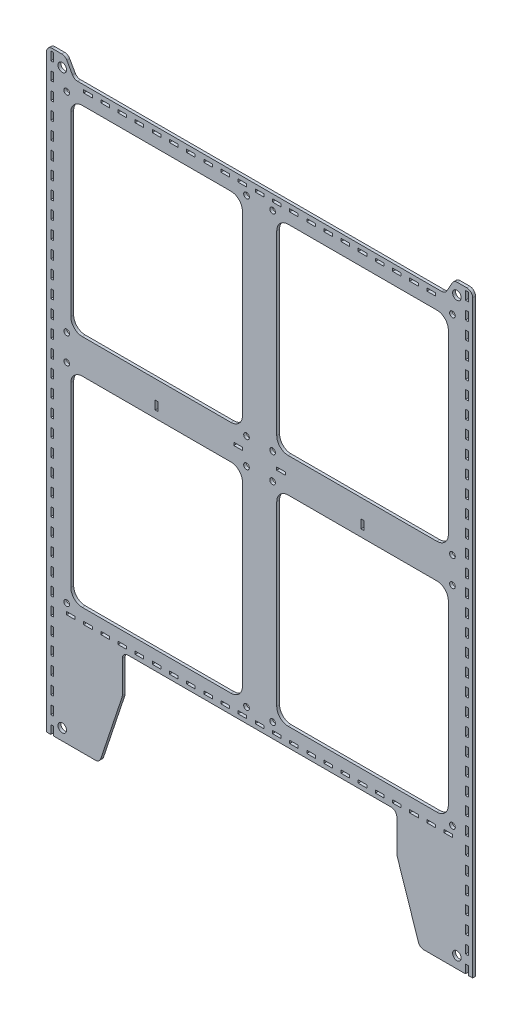
SolidWorks part; units mm, degrees
material "ABS"
ref_plane "Front Plane" through (0, 0, 0) normal (0, 0, 1) x (1, 0, 0)
ref_plane "Top Plane" through (0, 0, 0) normal (0, 1, 0) x (1, 0, 0)
ref_plane "Right Plane" through (0, 0, 0) normal (1, 0, 0) x (0, 0, -1)
sketch "Sketch1" plane through (0, 0, 0) normal (0, 0, 1) x (1, 0, 0)
  line L1 (-114.3, -127) -> (114.3, -127)
  line L2 (-114.3, -127) -> (-114.3, 127)
  line L3 (-114.3, 127) -> (114.3, 127)
  line L4 (114.3, -127) -> (114.3, 127)
  line L5 (-114.3, -127) -> (114.3, 127) construction
  line L6 (-114.3, 127) -> (114.3, -127) construction
  point P0 (0, 0)
  dimension "D1" = 254
  dimension "D2" = 228.6
extrude "Boss-Extrude1" add sketch "Sketch1" along normal mid plane 1.5875
sketch "Sketch2" plane through (0, 0, 0.7937) normal (0, 0, 1) x (1, 0, 0)
  line L0 (-114.3, -127) -> (-114.3, -190.5)
  line L1 (-114.3, -190.5) -> (-88.9, -190.5)
  line L2 (-88.9, -190.5) -> (-76.2, -152.4)
  line L3 (-76.2, -152.4) -> (-76.2, -127)
  line L4 (-114.3, -127) -> (114.3, -127) construction
  line L5 (-76.2, -127) -> (-114.3, -127)
  line L6 (114.3, -127) -> (114.3, -190.5)
  line L7 (114.3, -190.5) -> (88.9, -190.5)
  line L8 (88.9, -190.5) -> (76.2, -152.4)
  line L9 (76.2, -152.4) -> (76.2, -127)
  line L10 (114.3, -127) -> (76.2, -127)
  line L11 (-114.3, 127) -> (-114.3, 139.7)
  line L12 (-114.3, 139.7) -> (-107.95, 139.7)
  line L13 (-107.95, 139.7) -> (-101.6, 128.5875)
  line L14 (114.3, 127) -> (-114.3, 127) construction
  line L15 (-101.6, 127) -> (-114.3, 127)
  line L16 (114.3, 127) -> (114.3, 139.7)
  line L17 (114.3, 139.7) -> (107.95, 139.7)
  line L18 (-101.6, 128.5875) -> (-101.6, 127)
  line L19 (101.6, 127) -> (114.3, 127)
  line L20 (107.95, 139.7) -> (101.6, 128.5875)
  line L21 (101.6, 128.5875) -> (101.6, 127)
  dimension "D1" = 63.5
  dimension "D2" = 25.4
  dimension "D3" = 25.4
  dimension "D4" = 38.1
  dimension "D5" = 12.7
  dimension "D6" = 6.35
  dimension "D7" = 12.7
  dimension "D8" = 1.5875
extrude "Boss-Extrude2" add sketch "Sketch2" against normal up to surface (1.5875 mm away) up to face at (0, 0, -0.7937)
sketch "Sketch7" plane through (0, 0, 0.7937) normal (0, 0, 1) x (1, 0, 0)
  line L0 (-114.3, 139.7) -> (-118.2688, 139.7)
  line L1 (-118.2688, 139.7) -> (-118.2688, 130.175)
  line L2 (-118.2688, 130.175) -> (-114.3, 130.175)
  line L3 (-114.3, 139.7) -> (-114.3, -190.5) construction
  line L4 (-114.3, 130.175) -> (-114.3, 133.35)
  line L5 (-114.3, 133.35) -> (-115.8875, 133.35)
  line L6 (-115.8875, 133.35) -> (-115.8875, 138.1125)
  line L7 (-115.8875, 138.1125) -> (-114.3, 138.1125)
  line L8 (-114.3, 138.1125) -> (-114.3, 139.7)
  dimension "D1" = 1.5875
  dimension "D2" = 3.175
  dimension "D3" = 2.3813
  dimension "D4" = 1.5875
  dimension "D5" = 4.7625
extrude "Boss-Extrude6" add sketch "Sketch7" against normal up to surface (1.5875 mm away) up to face at (1.5875, -16.5199, -0.7937)
pattern_linear "LPattern3" count 34 spacing 9.525 along (0, -1, 0) of "Boss-Extrude6"
sketch "Sketch10" plane through (0, 0, 0.7937) normal (0, 0, 1) x (1, 0, 0)
  line L0 (-118.2688, -190.5) -> (-115.8875, -190.5)
  line L1 (-115.8875, -190.5) -> (-115.8875, -185.7375)
  line L2 (-115.8875, -185.7375) -> (-114.3, -185.7375)
  line L3 (-114.3, -184.15) -> (-114.3, -190.5) construction
  line L4 (-114.3, -185.7375) -> (-114.3, -184.15)
  line L5 (-114.3, -184.15) -> (-118.2688, -184.15)
  line L6 (-118.2688, -184.15) -> (-118.2688, -190.5)
  line L7 (-115.8875, -180.975) -> (-115.8875, -176.2125) construction
  line L8 (-114.3, -190.5) -> (-88.9, -190.5) construction
  dimension "D1" = 1.5875
extrude "Boss-Extrude9" add sketch "Sketch10" against normal up to surface (1.5875 mm away) up to face at (-115.0938, 126.2062, -0.7937)
mirror "Mirror3" about plane through (0, 0, 0) normal (1, 0, 0) of "Boss-Extrude9", "LPattern3"
sketch "Sketch8" plane through (0, 0, 0.7937) normal (0, 0, 1) x (1, 0, 0)
  line L0 (-101.6, 130.9688) -> (-92.075, 130.9688)
  line L1 (-92.075, 130.9688) -> (-92.075, 127)
  line L2 (101.6, 127) -> (-101.6, 127) construction
  line L3 (-92.075, 127) -> (-92.8688, 127)
  line L4 (-92.8688, 127) -> (-92.8688, 128.5875)
  line L5 (-92.8688, 128.5875) -> (-97.6313, 128.5875)
  line L6 (-97.6313, 128.5875) -> (-97.6313, 127)
  line L7 (-97.6313, 127) -> (-101.6, 127)
  line L8 (-101.6, 127) -> (-101.6, 130.9688)
  dimension "D1" = 3.9688
  dimension "D2" = 1.5875
  dimension "D3" = 4.7625
  dimension "D4" = 2.3813
  dimension "D5" = 0.7937
extrude "Boss-Extrude7" add sketch "Sketch8" against normal up to surface (1.5875 mm away) up to face at (1.0583, -73.7195, -0.7937)
pattern_linear "LPattern4" count 22 spacing 9.525 along (1, 0, 0) of "Boss-Extrude7"
sketch "Sketch9" plane through (0, 0, 0.7937) normal (0, 0, 1) x (1, 0, 0)
  line L0 (-101.6, 130.9688) -> (-102.9607, 130.9688)
  line L1 (-101.6, 128.5875) -> (-107.95, 139.7) construction
  line L2 (-102.9607, 130.9688) -> (-101.6, 128.5875)
  line L3 (-101.6, 128.5875) -> (-101.6, 130.9688)
extrude "Boss-Extrude8" add sketch "Sketch9" against normal up to surface (1.5875 mm away) up to face at (-85.1297, 127.7937, -0.7937)
mirror "Mirror4" about plane through (0, 0, 0) normal (0, 1, 0) of "LPattern4"
sketch "Sketch13" plane through (0, 0, 0.7937) normal (0, 0, 1) x (1, 0, 0)
  line L0 (-73.8188, -128.5875) -> (-73.8188, -127) construction
  line L1 (-76.2, -127) -> (-78.5813, -127)
  line L2 (-76.2, -127) -> (-76.2, -128.5875)
  line L3 (-76.2, -128.5875) -> (-78.5813, -128.5875)
  line L4 (-78.5813, -127) -> (-78.5813, -128.5875)
  line L5 (-83.3438, -127) -> (-88.1063, -127)
  line L6 (-83.3438, -127) -> (-83.3438, -128.5875)
  line L7 (-83.3438, -128.5875) -> (-88.1063, -128.5875)
  line L8 (-88.1063, -127) -> (-88.1063, -128.5875)
  line L9 (-76.2, -128.5875) -> (-73.8188, -128.5875) construction
  line L11 (-92.8688, -127) -> (-97.6313, -127)
  line L12 (-92.8688, -127) -> (-92.8688, -128.5875)
  line L13 (-92.8688, -128.5875) -> (-97.6313, -128.5875)
  line L14 (-97.6313, -127) -> (-97.6313, -128.5875)
  line L15 (-102.3938, -127) -> (-107.1563, -127)
  line L16 (-102.3938, -127) -> (-102.3938, -128.5875)
  line L17 (-102.3938, -128.5875) -> (-107.1563, -128.5875)
  line L18 (-107.1563, -127) -> (-107.1563, -128.5875)
  dimension "D1" = 4.7625
  dimension "D2" = 4.7625
  dimension "D3" = 4.7625
  dimension "D4" = 4.7625
  dimension "D5" = 4.7625
extrude "Cut-Extrude2" cut sketch "Sketch13" against normal through all
mirror "Mirror5" about plane through (0, 0, 0) normal (1, 0, 0) of "Cut-Extrude2"
sketch "Sketch18" plane through (0, 0, 0.7937) normal (0, 0, 1) x (1, 0, 0)
  line L1 (-0.7938, -5.5562) -> (0.7938, -5.5562) construction
  line L2 (-0.7938, -5.5562) -> (-0.7938, -0.7937) construction
  line L3 (-0.7938, -0.7937) -> (0.7938, -0.7937) construction
  line L4 (0.7938, -5.5562) -> (0.7938, -0.7937) construction
  line L5 (-0.7938, -5.5562) -> (0.7938, -0.7937) construction
  line L6 (-0.7938, -0.7937) -> (0.7938, -5.5562) construction
  line L7 (56.3563, -5.5563) -> (57.9437, -5.5563)
  line L8 (56.3563, -5.5563) -> (56.3563, -0.7938)
  line L9 (56.3563, -0.7938) -> (57.9437, -0.7938)
  line L10 (57.9437, -5.5563) -> (57.9437, -0.7938)
  line L11 (56.3563, -5.5563) -> (57.9437, -0.7938) construction
  line L12 (56.3563, -0.7938) -> (57.9437, -5.5563) construction
  line L13 (-56.3563, -5.5563) -> (-57.9438, -5.5563)
  line L14 (-56.3563, -5.5563) -> (-56.3563, -0.7938)
  line L15 (-56.3563, -0.7938) -> (-57.9438, -0.7938)
  line L16 (-57.9438, -5.5563) -> (-57.9438, -0.7938)
  line L17 (-56.3563, -5.5563) -> (-57.9438, -0.7938) construction
  line L18 (-56.3563, -0.7938) -> (-57.9438, -5.5563) construction
  point P0 (0, -3.175)
  point P6 (57.15, -3.175)
  point P11 (-57.15, -3.175)
  dimension "D1" = 1.5875
  dimension "D2" = 4.7625
  dimension "D3" = 57.15
  dimension "D4" = 57.15
  dimension "D5" = 0.7937
extrude "Cut-Extrude4" cut sketch "Sketch18" against normal through all
sketch "Sketch19" plane through (0, 0, 0.7937) normal (0, 0, 1) x (1, 0, 0)
  line L0 (-9.525, -9.525) -> (9.525, 9.525) construction
  line L1 (-104.775, 9.525) -> (-9.525, 9.525)
  line L2 (-104.775, 9.525) -> (-104.775, 120.65)
  line L3 (-104.775, 120.65) -> (-9.525, 120.65)
  line L4 (-9.525, 9.525) -> (-9.525, 120.65)
  line L5 (-104.775, 9.525) -> (-9.525, 120.65) construction
  line L6 (-104.775, 120.65) -> (-9.525, 9.525) construction
  line L7 (9.525, 9.525) -> (104.775, 9.525)
  line L8 (9.525, 9.525) -> (9.525, 120.65)
  line L9 (9.525, 120.65) -> (104.775, 120.65)
  line L10 (104.775, 9.525) -> (104.775, 120.65)
  line L11 (9.525, 9.525) -> (104.775, 120.65) construction
  line L12 (9.525, 120.65) -> (104.775, 9.525) construction
  line L13 (9.525, -9.525) -> (104.775, -9.525)
  line L14 (9.525, -9.525) -> (9.525, -120.65)
  line L15 (9.525, -120.65) -> (104.775, -120.65)
  line L16 (104.775, -9.525) -> (104.775, -120.65)
  line L17 (9.525, -9.525) -> (104.775, -120.65) construction
  line L18 (9.525, -120.65) -> (104.775, -9.525) construction
  line L19 (-9.525, -9.525) -> (-104.775, -9.525)
  line L20 (-9.525, -9.525) -> (-9.525, -120.65)
  line L21 (-9.525, -120.65) -> (-104.775, -120.65)
  line L22 (-104.775, -9.525) -> (-104.775, -120.65)
  line L23 (-9.525, -9.525) -> (-104.775, -120.65) construction
  line L24 (-9.525, -120.65) -> (-104.775, -9.525) construction
  point P0 (-57.15, 65.0875)
  point P5 (57.15, 65.0875)
  point P10 (57.15, -65.0875)
  point P15 (-57.15, -65.0875)
  dimension "D1" = 209.55
  dimension "D2" = 241.3
  dimension "D3" = 19.05
  dimension "D4" = 19.05
extrude "Cut-Extrude5" cut sketch "Sketch19" against normal through all
fillet "Fillet1" radius 6.35 16 edges at (-104.775, -120.65, 0) (-9.525, -120.65, 0) (-9.525, -9.525, 0) (-104.775, -9.525, 0) (104.775, -9.525, 0) (9.525, -9.525, 0) (9.525, -120.65, 0) (104.775, -120.65, 0) (104.775, 120.65, 0) (9.525, 120.65, 0) (9.525, 9.525, 0) (104.775, 9.525, 0) (-9.525, 120.65, 0) (-104.775, 120.65, 0) (-104.775, 9.525, 0) (-9.525, 9.525, 0)
sketch "Sketch20" plane through (0, 0, 0.7937) normal (0, 0, 1) x (1, 0, 0)
  line L0 (-9.525, 0.7938) -> (9.525, -0.7938) construction
  line L1 (-14.2875, -0.7938) -> (-9.525, -0.7938)
  line L2 (-14.2875, -0.7938) -> (-14.2875, 0.7938)
  line L3 (-14.2875, 0.7938) -> (-9.525, 0.7938)
  line L4 (-9.525, -0.7938) -> (-9.525, 0.7938)
  line L5 (-14.2875, -0.7938) -> (-9.525, 0.7938) construction
  line L6 (-14.2875, 0.7938) -> (-9.525, -0.7938) construction
  line L7 (9.525, -0.7938) -> (14.2875, -0.7938)
  line L8 (9.525, -0.7938) -> (9.525, 0.7938)
  line L9 (9.525, 0.7938) -> (14.2875, 0.7938)
  line L10 (14.2875, -0.7938) -> (14.2875, 0.7938)
  line L11 (9.525, -0.7938) -> (14.2875, 0.7938) construction
  line L12 (9.525, 0.7938) -> (14.2875, -0.7938) construction
  point P0 (-11.9062, 0)
  point P5 (11.9062, 0)
  dimension "D1" = 4.7625
  dimension "D2" = 19.05
  dimension "D3" = 1.5875
extrude "Cut-Extrude6" cut sketch "Sketch20" against normal through all
sketch "Sketch21" plane through (0, 0, 0.7937) normal (0, 0, 1) x (1, 0, 0)
  line L1 (-109.5375, -184.15) -> (109.5375, -184.15) construction
  line L2 (-109.5375, -184.15) -> (-109.5375, 133.35) construction
  line L3 (-109.5375, 133.35) -> (109.5375, 133.35) construction
  line L4 (109.5375, -184.15) -> (109.5375, 133.35) construction
  line L5 (-109.5375, -184.15) -> (109.5375, 133.35) construction
  line L6 (-109.5375, 133.35) -> (109.5375, -184.15) construction
  line L8 (-107.95, 139.7) -> (-118.2688, 139.7) construction
  line L9 (-114.3, 138.1125) -> (-114.3, 133.35) construction
  line L10 (-114.3, -190.5) -> (-88.9, -190.5) construction
  circle A0 centre (-109.5375, 133.35) radius 2.3813
  circle A1 centre (-109.5375, -184.15) radius 2.3813
  circle A2 centre (109.5375, 133.35) radius 2.3813
  circle A3 centre (109.5375, -184.15) radius 2.3813
  point P0 (0, -25.4)
  dimension "D2" = 4.7625
  dimension "D1" = 6.35
  dimension "D3" = 4.7625
  dimension "D4" = 6.35
extrude "Cut-Extrude7" cut sketch "Sketch21" against normal through all
sketch "Sketch22" plane through (0, 0, 0.7937) normal (0, 0, 1) x (1, 0, 0)
  line L0 (-107.061, 15.875) -> (-107.061, 7.239) construction
  line L1 (-107.061, 7.239) -> (-98.425, 7.239) construction
  line L2 (-15.875, 7.239) -> (-7.239, 7.239) construction
  line L3 (-7.239, 7.239) -> (-7.239, 15.875) construction
  line L4 (-7.239, 15.875) -> (-6.626, 15.9261)
  line L5 (-7.239, 114.3) -> (-7.239, 122.936) construction
  line L6 (-7.239, 122.936) -> (-15.875, 122.936) construction
  line L7 (-98.425, 122.936) -> (-107.061, 122.936) construction
  line L8 (-107.061, 122.936) -> (-107.061, 114.3) construction
  line L9 (0, 130.9688) -> (0, -130.9688) construction
  line L10 (102.9607, 130.9688) -> (-102.9607, 130.9688) construction
  line L11 (76.2, -130.9688) -> (-76.2, -130.9688) construction
  line L12 (-118.2688, 0) -> (118.2688, 0) construction
  line L14 (-118.2688, 139.7) -> (-118.2688, -190.5) construction
  line L16 (118.2688, 139.7) -> (118.2688, -190.5) construction
  line L25 (-98.425, 7.239) -> (-15.875, 7.239)
  line L26 (-7.239, 15.875) -> (-7.239, 114.3)
  line L27 (-15.875, 122.936) -> (-98.425, 122.936)
  line L28 (-107.061, 114.3) -> (-107.061, 15.875)
  line L29 (-98.425, 7.239) -> (-15.875, 7.239) construction
  line L30 (-7.239, 15.875) -> (-7.239, 114.3) construction
  line L31 (-15.875, 122.936) -> (-98.425, 122.936) construction
  line L32 (-107.061, 114.3) -> (-107.061, 15.875) construction
  circle A0 centre (-107.061, 122.936) radius 1.5748
  circle A1 centre (-7.239, 122.936) radius 1.5748
  circle A2 centre (-7.239, 7.239) radius 1.5748
  circle A3 centre (-107.061, 7.239) radius 1.5748
  circle A4 centre (7.239, 7.239) radius 1.5748
  circle A5 centre (107.061, 7.239) radius 1.5748
  circle A6 centre (7.239, 122.936) radius 1.5748
  circle A7 centre (107.061, 122.936) radius 1.5748
  circle A8 centre (107.061, -122.936) radius 1.5748
  circle A9 centre (7.239, -122.936) radius 1.5748
  circle A10 centre (107.061, -7.239) radius 1.5748
  circle A11 centre (7.239, -7.239) radius 1.5748
  circle A12 centre (-7.239, -7.239) radius 1.5748
  circle A13 centre (-107.061, -7.239) radius 1.5748
  circle A14 centre (-7.239, -122.936) radius 1.5748
  circle A15 centre (-107.061, -122.936) radius 1.5748
  arc A19 (-107.061, 15.875) -> (-98.425, 7.239) centre (-98.425, 15.875) ccw
  arc A20 (-15.875, 7.239) -> (-7.239, 15.875) centre (-15.875, 15.875) ccw
  arc A21 (-7.239, 114.3) -> (-15.875, 122.936) centre (-15.875, 114.3) ccw
  arc A22 (-98.425, 122.936) -> (-107.061, 114.3) centre (-98.425, 114.3) ccw
  dimension "D2" = 3.1496
  dimension "D1" = 2.286
extrude "Cut-Extrude8" cut sketch "Sketch22" against normal through all contours A0 | A1 | A6 | A7 | A5 | A10 | A11 | A4 | A2 | A12 | A13 | A3 | A15 | A14 | A9 | A8 region at (-107.061, 122.936, 0.7937) region at (-7.239, 122.936, 0.7937) region at (-7.239, 7.239, 0.7937) region at (-107.061, 7.239, 0.7937) region at (7.239, 7.239, 0.7937) region at (107.061, 7.239, 0.7937) region at (7.239, 122.936, 0.7937) region at (107.061, 122.936, 0.7937) region at (107.061, -122.936, 0.7937) region at (7.239, -122.936, 0.7937) region at (107.061, -7.239, 0.7937) region at (7.239, -7.239, 0.7937) region at (-7.239, -7.239, 0.7937) region at (-107.061, -7.239, 0.7937) region at (-7.239, -122.936, 0.7937) region at (-107.061, -122.936, 0.7937)
fillet "Fillet2" radius 3.175 6 edges at (88.9, -190.5, 0) (76.2, -152.4, 0) (76.2, -130.9688, 0) (-76.2, -130.9688, 0) (-76.2, -152.4, 0) (-88.9, -190.5, 0)
fillet "Fillet3" radius 3.175 6 edges at (118.2688, 139.7, 0) (107.95, 139.7, 0) (102.9607, 130.9688, 0) (-102.9607, 130.9688, 0) (-107.95, 139.7, 0) (-118.2688, 139.7, 0)
